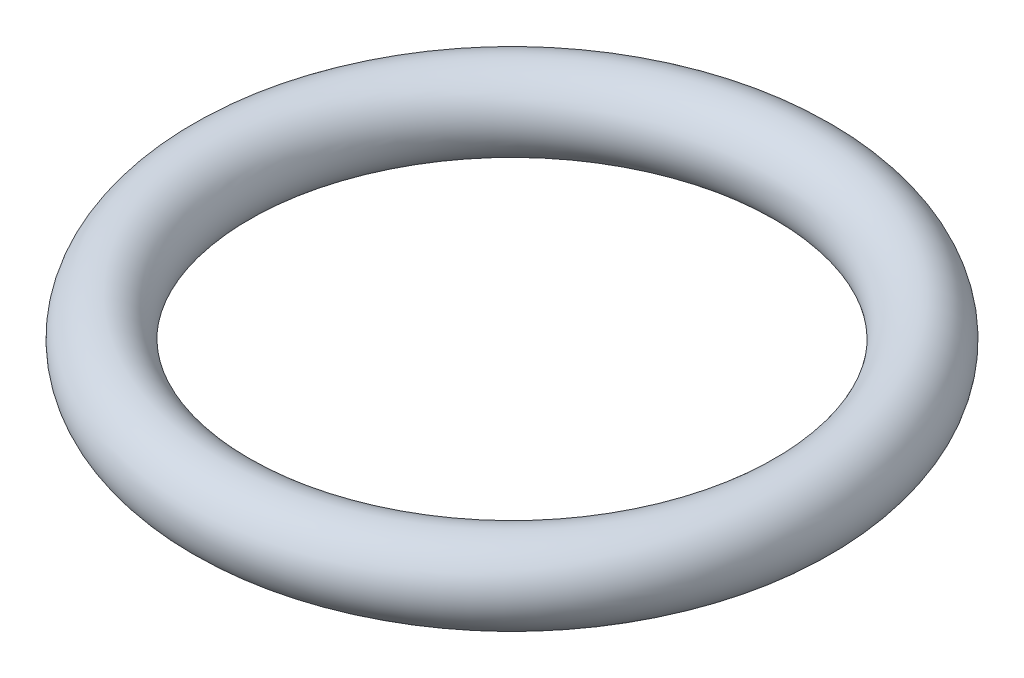
SolidWorks part; units mm, degrees
material "NBR"
ref_plane "Plano frontal" through (0, 0, 0) normal (0, 0, 1) x (1, 0, 0)
ref_plane "Plano superior" through (0, 0, 0) normal (0, 1, 0) x (1, 0, 0)
ref_plane "Plano direito" through (0, 0, 0) normal (1, 0, 0) x (0, 0, -1)
sketch "Esboço1" plane through (0, 0, 0) normal (0, 0, 1) x (1, 0, 0)
  line L0 (0, 0) -> (5.55, 0) construction
  line L1 (0, 0) -> (0, 2) construction
  circle A0 centre (5.55, 0) radius 0.75
  dimension "D1" = 1.5
  dimension "D2" = 5.55
  dimension "D3" = 2
sketch "Esboço2" plane through (0, 0, 0) normal (1, 0, 0) x (0, 0, -1)
  line L1 (0, 0) -> (0, 1) construction
  point P0 (0, 0.5)
  dimension "D1" = 1
revolve "Revolução1" add sketch "Esboço1" angle 360 about L1
